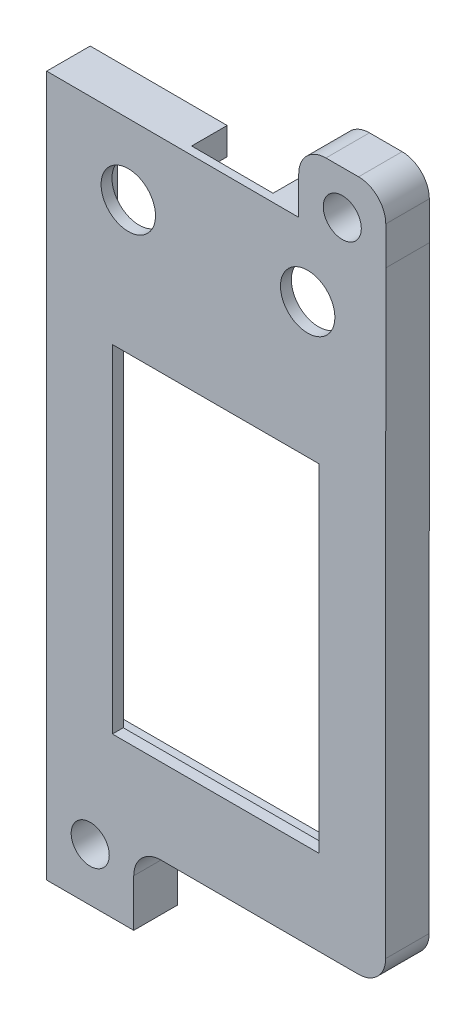
SolidWorks part; units mm, degrees
ref_plane "Front" through (0, 0, 0) normal (0, 0, 1) x (1, 0, 0)
ref_plane "Top" through (0, 0, 0) normal (0, 1, 0) x (1, 0, 0)
ref_plane "Side" through (0, 0, 0) normal (1, 0, 0) x (0, 0, -1)
ref_axis "X_Axis" through (-20.1896, 0, 0) along (1, 0, 0)
ref_axis "Y_Axis" through (0, -14.8261, 0) along (0, 1, 0)
ref_axis "Z_Axis" through (0, 0, -19.842) along (0, 0, 1)
sketch "Sketch1" plane through (0, 0, 0) normal (0, 0, 1) x (1, 0, 0)
  line L0 (-13.6902, 17.3557) -> (12.4596, 17.3297) construction
  line L1 (12.4596, 17.3297) -> (12.4719, 69.814) construction
  line L2 (12.4719, 69.814) -> (-13.6902, 69.8802) construction
  line L3 (-13.6902, 69.8802) -> (-13.6902, 17.3557) construction
  line L4 (-13.6902, 17.3557) -> (12.4596, 17.3297)
  line L5 (12.4596, 17.3297) -> (12.4719, 69.814)
  line L6 (12.4719, 69.814) -> (-13.6902, 69.8802)
  line L7 (-13.6902, 69.8802) -> (-13.6902, 17.3557)
  line L8 (-5.6878, 14.8478) -> (12.4572, 14.8297)
  line L9 (14.9596, 17.3291) -> (14.9725, 72.3076)
  line L10 (-16.1902, 8) -> (-8.1902, 8)
  line L11 (-16.1902, 8) -> (-8.1902, 8)
  line L13 (6.9725, 72.3279) -> (-16.1902, 72.3865)
  line L14 (-16.1902, 72.3865) -> (-16.1902, 8)
  line L15 (-8.1902, 8) -> (-8.1902, 12.3478)
  line L16 (-5.6878, 14.8478) -> (12.4572, 14.8297)
  line L17 (14.9596, 17.3291) -> (14.9725, 72.3076)
  line L21 (6.9725, 72.3279) -> (-16.1902, 72.3865)
  line L22 (-16.1902, 72.3865) -> (-16.1902, 8)
  line L23 (-8.1902, 8) -> (-8.1902, 12.3478)
  line L62 (14.9725, 72.3076) -> (14.9725, 75.8076)
  line L63 (14.9725, 72.3076) -> (14.9725, 75.8076)
  line L64 (12.4725, 78.3076) -> (9.4725, 78.3076)
  line L65 (12.4725, 78.3076) -> (9.4725, 78.3076)
  line L66 (6.9725, 75.8076) -> (6.9725, 72.3279)
  line L67 (6.9725, 75.8076) -> (6.9725, 72.3279)
  circle A1 centre (10.9729, 74.3178) radius 1.75
  circle A3 centre (-12.1902, 12.8542) radius 1.75
  arc A5 (12.4572, 14.8297) -> (14.9596, 17.3291) centre (12.4596, 17.3297) ccw
  arc A9 (-5.6878, 14.8478) -> (-8.1902, 12.3478) centre (-5.6902, 12.3478) ccw
  arc A10 (12.4572, 14.8297) -> (14.9596, 17.3291) centre (12.4596, 17.3297) ccw
  arc A14 (-5.6878, 14.8478) -> (-8.1902, 12.3478) centre (-5.6902, 12.3478) ccw
  circle A19 centre (10.9729, 74.3178) radius 2 construction
  circle A20 centre (-12.1902, 12.8542) radius 2 construction
  arc A33 (14.9725, 75.8076) -> (12.4725, 78.3076) centre (12.4725, 75.8076) ccw
  arc A34 (14.9725, 75.8076) -> (12.4725, 78.3076) centre (12.4725, 75.8076) ccw
  arc A35 (9.4725, 78.3076) -> (6.9725, 75.8076) centre (9.4725, 75.8076) ccw
  arc A36 (9.4725, 78.3076) -> (6.9725, 75.8076) centre (9.4725, 75.8076) ccw
  dimension "D2" = 3.5
  dimension "D3" = 3.5
  dimension "D1" = 0
extrude "Boss-Extrude1" add sketch "Sketch1" along normal blind 1
sketch "Sketch2" plane through (0, 0, 1) normal (0, 0, 1) x (1, 0, 0)
  line L0 (12.4596, 17.3297) -> (12.4719, 69.814) construction
  line L3 (-13.6902, 21.3306) -> (12.4606, 21.3306)
  line L5 (12.4719, 69.814) -> (-13.6902, 69.8802) construction
  line L6 (-13.6902, 69.8802) -> (-13.6902, 17.3557) construction
  line L7 (12.4606, 21.3306) -> (12.4719, 69.814)
  line L8 (12.4719, 69.814) -> (-13.6902, 69.8802)
  line L9 (-13.6902, 69.8802) -> (-13.6902, 21.3306)
  line L13 (-5.6878, 14.8478) -> (12.4572, 14.8297)
  line L14 (14.9596, 17.3291) -> (14.9725, 72.3076)
  line L18 (6.9725, 72.3279) -> (-16.1902, 72.3865)
  line L19 (-16.1902, 72.3865) -> (-16.1902, 8)
  line L20 (-8.1902, 8) -> (-8.1902, 12.3478)
  line L21 (-5.6878, 14.8478) -> (12.4572, 14.8297)
  line L22 (14.9596, 17.3291) -> (14.9725, 72.3076)
  line L26 (6.9725, 72.3279) -> (-16.1902, 72.3865)
  line L27 (-16.1902, 72.3865) -> (-16.1902, 8)
  line L28 (-8.1902, 8) -> (-8.1902, 12.3478)
  line L32 (14.9725, 72.3076) -> (14.9725, 75.8076)
  line L33 (14.9725, 72.3076) -> (14.9725, 75.8076)
  line L34 (12.4725, 78.3076) -> (9.4725, 78.3076)
  line L35 (12.4725, 78.3076) -> (9.4725, 78.3076)
  line L36 (6.9725, 75.8076) -> (6.9725, 72.3279)
  line L37 (6.9725, 75.8076) -> (6.9725, 72.3279)
  circle A0 centre (10.9729, 74.3178) radius 1.75 construction
  circle A1 centre (10.9729, 74.3178) radius 1.75
  circle A2 centre (-12.1902, 12.8542) radius 1.75 construction
  circle A3 centre (-12.1902, 12.8542) radius 1.75
  arc A5 (-5.6878, 14.8478) -> (-8.1902, 12.3478) centre (-5.6902, 12.3478) ccw
  arc A6 (12.4572, 14.8297) -> (14.9596, 17.3291) centre (12.4596, 17.3297) ccw
  arc A10 (-5.6878, 14.8478) -> (-8.1902, 12.3478) centre (-5.6902, 12.3478) ccw
  arc A11 (12.4572, 14.8297) -> (14.9596, 17.3291) centre (12.4596, 17.3297) ccw
  arc A16 (14.9725, 75.8076) -> (12.4725, 78.3076) centre (12.4725, 75.8076) ccw
  arc A17 (14.9725, 75.8076) -> (12.4725, 78.3076) centre (12.4725, 75.8076) ccw
  arc A18 (9.4725, 78.3076) -> (6.9725, 75.8076) centre (9.4725, 75.8076) ccw
  arc A19 (9.4725, 78.3076) -> (6.9725, 75.8076) centre (9.4725, 75.8076) ccw
  spline S1 degree 1 poles (-3016.1683, 8) (2991.7739, 8) knots -374.997257 -374.997257 375.995518 375.995518 only from (-16.1902, 8) to (-8.1902, 8)
  spline S2 degree 1 poles (-16.1902, 8) (-8.1902, 8) knots 0 0 1 1
  dimension "D1" = 0
extrude "Boss-Extrude2" add sketch "Sketch2" along normal blind 2
sketch "Sketch3" plane through (0, 0, 3) normal (0, 0, 1) x (1, 0, 0)
  line L6 (-0.6521, 70.6723) -> (-0.6521, 14.8428) construction
  line L7 (2.5179, 70.6723) -> (-3.8221, 70.6723) construction
  line L8 (-5.6878, 14.8478) -> (12.4572, 14.8297)
  line L9 (14.9596, 17.3291) -> (14.9725, 72.3076)
  line L10 (14.9725, 72.3076) -> (14.9725, 75.8076)
  line L11 (12.4725, 78.3076) -> (9.4725, 78.3076)
  line L12 (6.9725, 75.8076) -> (6.9725, 72.3279)
  line L13 (6.9725, 72.3279) -> (-16.1902, 72.3865)
  line L14 (-16.1902, 72.3865) -> (-16.1902, 8)
  line L15 (-8.1902, 8) -> (-8.1902, 12.3478)
  line L16 (-5.6878, 14.8478) -> (12.4572, 14.8297)
  line L17 (14.9596, 17.3291) -> (14.9725, 72.3076)
  line L18 (14.9725, 72.3076) -> (14.9725, 75.8076)
  line L19 (12.4725, 78.3076) -> (9.4725, 78.3076)
  line L20 (6.9725, 75.8076) -> (6.9725, 72.3279)
  line L21 (6.9725, 72.3279) -> (-16.1902, 72.3865)
  line L22 (-16.1902, 72.3865) -> (-16.1902, 8)
  line L23 (-8.1902, 8) -> (-8.1902, 12.3478)
  line L25 (-10.0754, 67.8674) -> (-7.3068, 63.8796) construction
  line L26 (-7.3068, 67.8674) -> (-10.0754, 63.8796) construction
  line L27 (6.4092, 68.0198) -> (9.1778, 64.032) construction
  line L28 (8.8479, 53.6482) -> (-10.1521, 53.6482)
  line L29 (8.8479, 53.6482) -> (8.8479, 22.6482)
  line L30 (8.8479, 22.6482) -> (-10.1521, 22.6482)
  line L31 (-10.1521, 53.6482) -> (-10.1521, 22.6482)
  line L36 (9.1778, 68.0198) -> (9.1778, 64.032) construction
  line L37 (9.1778, 64.032) -> (9.1778, 68.0198) construction
  line L38 (9.1778, 68.0198) -> (6.4092, 64.032) construction
  line L39 (8.8479, 53.6482) -> (-10.1521, 22.6482) construction
  line L40 (8.8479, 22.6482) -> (-10.1521, 53.6482) construction
  circle A0 centre (-8.6911, 65.8735) radius 2.5
  circle A1 centre (7.7935, 66.0259) radius 2.5
  circle A2 centre (10.9729, 74.3178) radius 1.75 construction
  circle A3 centre (10.9729, 74.3178) radius 1.75
  circle A4 centre (-12.1902, 12.8542) radius 1.75 construction
  arc A5 (-5.6878, 14.8478) -> (-8.1902, 12.3478) centre (-5.6902, 12.3478) ccw
  arc A6 (12.4572, 14.8297) -> (14.9596, 17.3291) centre (12.4596, 17.3297) ccw
  arc A7 (14.9725, 75.8076) -> (12.4725, 78.3076) centre (12.4725, 75.8076) ccw
  arc A8 (9.4725, 78.3076) -> (6.9725, 75.8076) centre (9.4725, 75.8076) ccw
  arc A10 (-5.6878, 14.8478) -> (-8.1902, 12.3478) centre (-5.6902, 12.3478) ccw
  arc A11 (12.4572, 14.8297) -> (14.9596, 17.3291) centre (12.4596, 17.3297) ccw
  arc A12 (14.9725, 75.8076) -> (12.4725, 78.3076) centre (12.4725, 75.8076) ccw
  arc A13 (9.4725, 78.3076) -> (6.9725, 75.8076) centre (9.4725, 75.8076) ccw
  circle A15 centre (-12.1902, 12.8542) radius 1.75
  spline S1 degree 1 poles (-3016.1683, 8) (2991.7739, 8) knots -374.997257 -374.997257 375.995518 375.995518 only from (-16.1902, 8) to (-8.1902, 8)
  spline S2 degree 1 poles (-16.1902, 8) (-8.1902, 8) knots 0 0 1 1
  point P29 (-0.6521, 38.1482)
  dimension "D3" = 5
  dimension "D2" = 31
  dimension "D4" = 19
  dimension "D5" = 4
  dimension "D1" = 0
extrude "Boss-Extrude3" add sketch "Sketch3" along normal blind 1
sketch "Sketch5" plane through (-16.1902, 0, 0) normal (-1, 0, 0) x (0, 0, 1)
  line L0 (-1.0102, 47.7252) -> (-1.0102, 67.4902) construction
  line L1 (-1.0102, 55.1394) -> (2.5898, 55.1394)
  line L2 (-1.0102, 55.1394) -> (-1.0102, 59.7394)
  line L3 (-1.0102, 59.7394) -> (2.5898, 59.7394)
  line L4 (2.5898, 55.1394) -> (2.5898, 59.7394)
  line L5 (2.0418, 57.428) -> (-1.0102, 57.4394) construction
  line L6 (2.0418, 55.142) -> (2.0418, 59.714) construction
  dimension "D1" = 3.6
  dimension "D2" = 4.6
extrude "Cut-Extrude1" cut sketch "Sketch5" against normal blind 21
sketch "Sketch6" plane through (0.1831, 72.3451, 0) normal (0.0025, 1, 0) x (1, -0.0025, 0)
  line L1 (-3.7868, -3.2648) -> (3.6943, -3.2648)
  line L2 (-3.7868, -3.2648) -> (-3.7868, 0)
  line L3 (-3.7868, 0) -> (3.6943, 0)
  line L4 (3.6943, -3.2648) -> (3.6943, 0)
extrude "Cut-Extrude2" cut sketch "Sketch6" against normal blind 21
